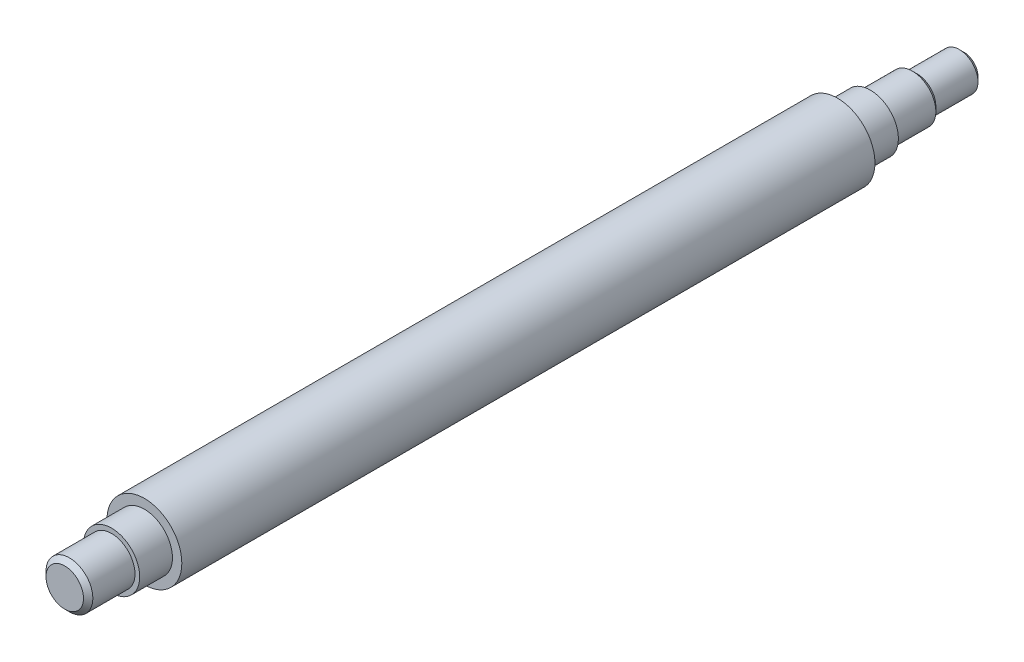
SolidWorks part; units mm, degrees
material "Ductile Iron (SN)"
ref_plane "Front Plane" through (0, 0, 0) normal (0, 0, 1) x (1, 0, 0)
ref_plane "Top Plane" through (0, 0, 0) normal (0, 1, 0) x (1, 0, 0)
ref_plane "Right Plane" through (0, 0, 0) normal (1, 0, 0) x (0, 0, -1)
sketch "Sketch1" plane through (0, 0, 0) normal (0, 0, 1) x (1, 0, 0)
  circle A0 centre (0, 0) radius 8
  dimension "D1" = 16
extrude "Boss-Extrude1" add sketch "Sketch1" along normal blind 148
sketch "Sketch4" plane through (0, 0, 0) normal (0, 0, 1) x (1, 0, 0)
  circle A0 centre (0, 0) radius 6
  dimension "D1" = 12
sketch "Sketch6" plane through (0, 0, 0) normal (0, 0, -1) x (-1, 0, 0)
  circle A0 centre (0, 0) radius 6
  dimension "D1" = 12
extrude "Boss-Extrude2" add sketch "Sketch6" along normal blind 5
sketch "Sketch7" plane through (0, 0, -5) normal (0, 0, -1) x (-1, 0, 0)
  circle A0 centre (0, 0) radius 6
  dimension "D1" = 12
extrude "Boss-Extrude3" add sketch "Sketch7" along normal blind 2
sketch "Sketch8" plane through (0, 0, -7) normal (0, 0, -1) x (-1, 0, 0)
  circle A0 centre (0, 0) radius 5
  dimension "D1" = 10
extrude "Boss-Extrude4" add sketch "Sketch8" along normal blind 10
sketch "Sketch9" plane through (0, 0, -17) normal (0, 0, -1) x (-1, 0, 0)
  circle A0 centre (0, 0) radius 4
  dimension "D1" = 8
extrude "Boss-Extrude5" add sketch "Sketch9" along normal blind 10
chamfer "Chamfer1" distance 1 angle 45 1 edges at (-5, 0, -17)
chamfer "Chamfer2" distance 1 angle 45 1 edges at (-4, 0, -27)
sketch "Sketch10" plane through (0, 0, 148) normal (0, 0, 1) x (1, 0, 0)
  circle A0 centre (0, 0) radius 6
  dimension "D1" = 12
extrude "Boss-Extrude6" add sketch "Sketch10" along normal blind 5
sketch "Sketch11" plane through (0, 0, 153) normal (0, 0, 1) x (1, 0, 0)
  circle A0 centre (0, 0) radius 6
  dimension "D1" = 12
extrude "Boss-Extrude7" add sketch "Sketch11" along normal blind 2
sketch "Sketch12" plane through (0, 0, 155) normal (0, 0, 1) x (1, 0, 0)
  circle A0 centre (0, 0) radius 5
  dimension "D1" = 10
extrude "Boss-Extrude8" add sketch "Sketch12" along normal blind 10
chamfer "Chamfer3" distance 1 angle 45 1 edges at (5, 0, 165)
